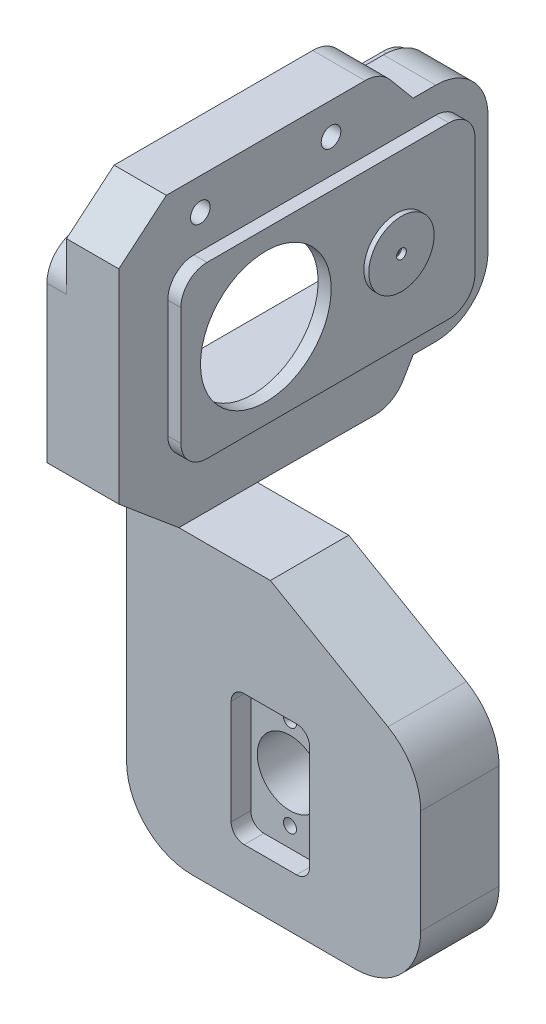
SolidWorks part; units mm, degrees
other "Markup1"
sketch "Sketch8" plane through (0, 0, -51.7836) normal (-1, 0, 0) x (0, 0, 1)
material "ABS"
ref_plane "Front Plane" through (0, 0, 0) normal (0, 0, 1) x (1, 0, 0)
ref_plane "Top Plane" through (0, 0, 0) normal (0, 1, 0) x (1, 0, 0)
ref_plane "Right Plane" through (0, 0, 0) normal (1, 0, 0) x (0, 0, -1)
sketch "Sketch1" plane through (0, 0, 0) normal (0, 0, 1) x (1, 0, 0)
  line L0 (0, 45) -> (0, 10)
  line L1 (10, 0) -> (35, 0)
  line L2 (45, 10) -> (45, 25.9474)
  line L3 (40, 34.6077) -> (22, 45)
  line L4 (22, 45) -> (0, 45)
  line L6 (18, 8) -> (26, 8)
  line L7 (16, 10) -> (16, 26)
  line L8 (18, 28) -> (26, 28)
  line L9 (28, 10) -> (28, 26)
  line L10 (16, 8) -> (28, 28) construction
  line L11 (16, 28) -> (28, 8) construction
  circle A0 centre (22, 18) radius 5
  circle A1 centre (22, 11) radius 1
  circle A2 centre (22, 25) radius 1
  arc A3 (18, 8) -> (16, 10) centre (18, 10) cw
  arc A4 (26, 8) -> (28, 10) centre (26, 10) ccw
  arc A5 (26, 28) -> (28, 26) centre (26, 26) cw
  arc A6 (16, 26) -> (18, 28) centre (18, 26) cw
  arc A11 (45, 25.9474) -> (40, 34.6077) centre (35, 25.9474) ccw
  arc A12 (0, 10) -> (10, 0) centre (10, 10) ccw
  arc A13 (35, 0) -> (45, 10) centre (35, 10) ccw
  point P44 (0, 0)
  point P47 (45, 0)
  dimension "D5" = 10
  dimension "D7" = 2
  dimension "D4" = 2
  dimension "D16" = 10
  dimension "D1" = 45
  dimension "D2" = 45
  dimension "D3" = 120
  dimension "D6" = 7
  dimension "D8" = 7
  dimension "D9" = 27
  dimension "D10" = 22
  dimension "D11" = 20
  dimension "D12" = 11
  dimension "D13" = 6
  dimension "D14" = 10
extrude "Boss-Extrude1" add sketch "Sketch1" against normal blind 12 contours L4 L0 A12 L1 A13 L2 A11 L3
extrude "Cut-Extrude1" cut sketch "Sketch1<3>" against normal blind 3 contours A2 | A6 L7 A3 L6 A4 L9 A5 L8 A2 A1 | A1 | A0 region at (16.7507, 8.7507, 0) region at (22, 11, 0) region at (22, 25, 0)
sketch "Sketch1<3>" plane through (0, 0, 0) normal (0, 0, 1) x (1, 0, 0) same geometry as "Sketch1"
extrude "Cut-Extrude2" cut sketch "Sketch1<4>" against normal through all contours A2 | A1 | A0 region at (22, 18, 0) region at (22, 11, 0) region at (22, 25, 0)
sketch "Sketch1<4>" plane through (0, 0, 0) normal (0, 0, 1) x (1, 0, 0) same geometry as "Sketch1"
sketch "Sketch3" plane through (0, 0, 0) normal (-1, 0, 0) x (0, 0, 1)
  line L0 (9.1925, 52.7135) -> (0, 45)
  line L1 (9.1925, 83.8935) -> (9.1925, 52.7135)
  line L2 (9.1925, 83.8935) -> (1.9151, 90)
  line L3 (1.9151, 90) -> (-28.4826, 90)
  line L4 (-32.3129, 88.2139) -> (-35.8509, 83.9975)
  line L6 (-41.3075, 76) -> (-41.3075, 58)
  line L8 (-34.3402, 47.4081) -> (-35.8509, 50)
  line L9 (-29.9998, 44.926) -> (-12, 45)
  line L10 (-0.3075, 76) -> (-0.3075, 58)
  line L15 (-47.3075, 75.9975) -> (-47.3075, 58)
  line L16 (-39.3075, 50) -> (-2.3075, 50)
  line L19 (5.6925, 75.9975) -> (5.6925, 58)
  line L21 (-12, 45) -> (0, 45)
  line L26 (-39.3075, 56) -> (-2.3075, 56)
  line L33 (-43.3075, 75.9975) -> (-43.3075, 58)
  line L34 (-39.3075, 54) -> (-2.3075, 54)
  line L35 (1.6925, 75.9975) -> (1.6925, 58)
  line L39 (-39.3075, 78) -> (-2.3075, 78)
  line L53 (-39.3075, 83.9975) -> (-2.3075, 83.9975)
  line L55 (-39.3075, 79.9975) -> (-2.3075, 79.9975)
  circle A0 centre (-11.3075, 67) radius 10
  arc A3 (-41.3075, 76) -> (-39.3075, 78) centre (-39.3075, 76) cw
  arc A5 (-34.3402, 47.4081) -> (-29.9998, 44.926) centre (-30.0204, 49.9259) ccw
  arc A12 (-43.3075, 75.9975) -> (-39.3075, 79.9975) centre (-39.3075, 75.9975) cw
  arc A14 (-0.3075, 58) -> (-2.3075, 56) centre (-2.3075, 58) cw
  arc A16 (-39.3075, 56) -> (-41.3075, 58) centre (-39.3075, 58) cw
  arc A21 (-43.3075, 58) -> (-39.3075, 54) centre (-39.3075, 58) ccw
  arc A22 (1.6925, 58) -> (-2.3075, 54) centre (-2.3075, 58) cw
  arc A23 (-2.3075, 79.9975) -> (1.6925, 75.9975) centre (-2.3075, 75.9975) cw
  arc A24 (-47.3075, 75.9975) -> (-39.3075, 83.9975) centre (-39.3075, 75.9975) cw
  circle A25 centre (-34.8075, 67) radius 5 construction
  arc A28 (-47.3075, 58) -> (-39.3075, 50) centre (-39.3075, 58) ccw
  arc A29 (-2.3075, 78) -> (-0.3075, 76) centre (-2.3075, 76) cw
  arc A32 (-28.4826, 90) -> (-32.3129, 88.2139) centre (-28.4826, 85) ccw
  arc A33 (5.6925, 58) -> (-2.3075, 50) centre (-2.3075, 58) cw
  arc A36 (-2.3075, 83.9975) -> (5.6925, 75.9975) centre (-2.3075, 75.9975) cw
  point P26 (-2.1748, 77.825)
  point P53 (-0.3075, 56.5128)
  line M15 (0, 45) -> (-12, 45)
  dimension "D4" = 11
  dimension "D13" = 130
  dimension "D15" = 53
  dimension "D18" = 10
  dimension "D8" = 25.9975
  dimension "D22" = 2
  dimension "D16" = 45
  dimension "D25" = 2
  dimension "D26" = 4
  dimension "D27" = 8
  dimension "D7" = 22
  dimension "D31" = 8
  dimension "D20" = 8
  dimension "D34" = 4
  dimension "D32" = 4
  dimension "D39" = 4
  dimension "D42" = 4
  dimension "D6" = 20
  dimension "D21" = 4
  dimension "D30" = 5
  dimension "D36" = 2
  dimension "D43" = 8
  dimension "D52" = 5
  dimension "D1" = 53
  dimension "D5" = 23.5
  dimension "D9" = 33.9975
  dimension "D10" = 45
  dimension "D11" = 45
  dimension "D12" = 9.5
  dimension "D14" = 12
  dimension "D17" = 41
  dimension "D19" = 6.5
  dimension "D24" = 4
  dimension "D28" = 12.5
  dimension "D29" = 5.5042
  dimension "D33" = 45
  dimension "D35" = 130
  dimension "D40" = 13
  dimension "D23" = 2
  dimension "D44" = 18
  dimension "D45" = 6
  dimension "D46" = 120
  dimension "D47" = 130
  dimension "D48" = 4
  dimension "D49" = 2
  dimension "D50" = 11
  dimension "D51" = 3
  dimension "D53" = 140
  dimension "D54" = 130
  dimension "D55" = 20.5
  dimension "D56" = 12.5
  dimension "D57" = 11
extrude "Boss-Extrude2" add sketch "Sketch3" against normal blind 8 contours L39 L10 L9 L0 L1 L2 L3 L4 M15 | L26 A0 L6 A3 L39 L10 | L19 L15 L16 L35 A22 L34 A21 L33 A12 region at (0, 49.3449, 4.1867) region at (0, 50.6297, -37.5792) region at (0, 78.4584, -41.7684)
extrude "Boss-Extrude3" add sketch "Sketch3<4>" against normal blind 10 contours A22 L35 A12 L33 A21 L34 L10 L26 L6 A3 L39 | L10 L39 A3 L6 L26 A0 | A0 region at (0, 67, -25.9144) region at (0, 78.4584, -41.7684) region at (0, 67, -11.3075)
sketch "Sketch3<4>" plane through (0, 0, 0) normal (-1, 0, 0) x (0, 0, 1) same geometry as "Sketch3"
extrude "Cut-Extrude5" cut sketch "Sketch3<6>" against normal blind 8 contours L26 L10 L39 A3 L6 A0 | A0 region at (0, 67, -25.9144) region at (0, 67, -11.3075)
sketch "Sketch3<6>" plane through (0, 0, 0) normal (-1, 0, 0) x (0, 0, 1) same geometry as "Sketch3"
extrude "Cut-Extrude6" cut sketch "Sketch3<7>" against normal through all contours A0 region at (0, 67, -11.3075)
sketch "Sketch3<7>" plane through (0, 0, 0) normal (-1, 0, 0) x (0, 0, 1) same geometry as "Sketch3"
sketch "Sketch7" plane through (0, 0, 0) normal (-1, 0, 0) x (0, 0, 1)
  line L0 (-41.3075, 76) -> (-41.3075, 58) construction
  line L1 (-0.3075, 76) -> (-0.3075, 58) construction
  line L2 (-39.3075, 56) -> (-2.3075, 56) construction
  circle A0 centre (-44.3075, 72) radius 1.2804
  circle A1 centre (-44.3075, 62) radius 1.2804
  circle A2 centre (2.6925, 62) radius 1.2804
  circle A3 centre (2.6925, 72) radius 1.2804
  dimension "D1" = 2.5608
  dimension "D2" = 3
  dimension "D3" = 3
  dimension "D4" = 3
  dimension "D5" = 10
  dimension "D6" = 6
extrude "Cut-Extrude7" cut sketch "Sketch7" against normal blind 3
sketch "Sketch11" plane through (8, 0, 0) normal (1, 0, 0) x (0, 0, -1)
  line L0 (39.3075, 79.9975) -> (2.3075, 79.9975) construction
  line L1 (-9.1925, 83.8935) -> (-9.1925, 52.7135) construction
  circle A0 centre (0.8075, 84.4975) radius 3
  circle A1 centre (24.8075, 84.4975) radius 3
  dimension "D1" = 6
  dimension "D5" = 6
  dimension "D2" = 4.5
  dimension "D3" = 24
  dimension "D4" = 10
sketch "Sketch9" plane through (8, 0, 0) normal (1, 0, 0) x (0, 0, -1)
  line L0 (13.2838, 90) -> (13.2838, 44.9947) construction
  line L1 (35.8509, 83.9975) -> (35.8509, 50) construction
  line L2 (39.3075, 79.9975) -> (2.3075, 79.9975) construction
  line L3 (-1.9151, 90) -> (28.4826, 90) construction
  line L4 (29.9998, 44.926) -> (12, 45) construction
  line L5 (47.3075, 66.9987) -> (-9.1925, 66.9987) construction
  line L6 (47.3075, 75.9975) -> (47.3075, 58) construction
  line L7 (-9.1925, 83.8935) -> (-9.1925, 52.7135) construction
  line L8 (19.0575, 90) -> (19.0575, 44.971) construction
  line L9 (13.3309, 90) -> (13.3309, 44.9945) construction
  circle A0 centre (3.2838, 85.1475) radius 1.5
  circle A1 centre (23.2838, 85.1475) radius 1.5
  dimension "D1" = 3
  dimension "D2" = 5.15
  dimension "D3" = 10
  dimension "D4" = 10
  dimension "D5" = 28.25
  dimension "D6" = 22.52
extrude "Cut-Extrude8" cut sketch "Sketch9" against normal through all both and the other way through all
sketch "Sketch12" plane through (10, 0, 0) normal (1, 0, 0) x (0, 0, -1)
  circle A0 centre (31.3075, 67) radius 0.5
  dimension "D1" = 1
  dimension "D2" = 20
extrude "Cut-Extrude9" cut sketch "Sketch12" against normal blind 10
sketch "Sketch13" plane through (10, 0, 0) normal (1, 0, 0) x (0, 0, -1)
  circle A0 centre (11.3075, 67) radius 10 construction
  circle A1 centre (31.3075, 67) radius 10 construction
  circle A2 centre (31.3075, 67) radius 5
  circle A3 centre (31.3075, 67) radius 0.75
  dimension "D1" = 20
  dimension "D2" = 10
  dimension "D3" = 1.5
extrude "Boss-Extrude5" add sketch "Sketch13" along normal blind 0.75 and the other way up to surface (2 mm away) other way up to face at (8, 67, -30.8075)
sketch "Sketch14" plane through (0, 0, 0) normal (-1, 0, 0) x (0, 0, 1)
  line L0 (-0.3075, 76) -> (-0.3075, 58) construction
  line L1 (-39.3075, 56) -> (-2.3075, 56) construction
  line L2 (-39.3075, 78) -> (-2.3075, 78) construction
  line L3 (-41.3075, 76) -> (-41.3075, 58) construction
  line L4 (-0.3075, 76) -> (-0.3075, 58)
  line L5 (-39.3075, 56) -> (-2.3075, 56)
  line L6 (-39.3075, 78) -> (-2.3075, 78)
  line L7 (-41.3075, 76) -> (-41.3075, 58)
  line L8 (-35.8509, 50) -> (5.9588, 50)
  line L9 (-45.1145, 81.5) -> (9.1925, 81.5)
  line L13 (0, 10) -> (0, 45)
  line L14 (0, 45) -> (9.1925, 52.7135)
  line L15 (9.1925, 52.7135) -> (9.1925, 83.8935)
  line L16 (9.1925, 83.8935) -> (1.9151, 90)
  line L17 (1.9151, 90) -> (-28.4826, 90)
  line L18 (-32.3129, 88.2139) -> (-35.8509, 83.9975)
  line L19 (-35.8509, 83.9975) -> (-39.3075, 83.9975)
  line L20 (-47.3075, 75.9975) -> (-47.3075, 58)
  line L21 (-39.3075, 50) -> (-35.8509, 50)
  line L22 (-35.8509, 50) -> (-34.3402, 47.4081)
  line L23 (-29.9998, 44.926) -> (-12, 45)
  line L24 (-12, 45) -> (-12, 10)
  line L25 (-12, 10) -> (0, 10)
  line L27 (5.9588, 50) -> (9.1925, 52.7135)
  line L28 (9.1925, 52.7135) -> (9.1925, 81.5)
  line L33 (-47.3075, 75.9975) -> (-47.3075, 58)
  line L34 (-39.3075, 50) -> (-35.8509, 50)
  arc A0 (-2.3075, 56) -> (-0.3075, 58) centre (-2.3075, 58) ccw construction
  arc A1 (-0.3075, 76) -> (-2.3075, 78) centre (-2.3075, 76) ccw construction
  arc A2 (-41.3075, 58) -> (-39.3075, 56) centre (-39.3075, 58) ccw construction
  arc A3 (-39.3075, 78) -> (-41.3075, 76) centre (-39.3075, 76) ccw construction
  arc A4 (-28.4826, 90) -> (-32.3129, 88.2139) centre (-28.4826, 85) ccw
  arc A5 (-39.3075, 83.9975) -> (-47.3075, 75.9975) centre (-39.3075, 75.9975) ccw
  arc A6 (-47.3075, 58) -> (-39.3075, 50) centre (-39.3075, 58) ccw
  arc A7 (-34.3402, 47.4081) -> (-29.9998, 44.926) centre (-30.0204, 49.9259) ccw
  arc A9 (-45.1145, 81.5) -> (-47.3075, 75.9975) centre (-39.3075, 75.9975) ccw
  arc A10 (-47.3075, 58) -> (-39.3075, 50) centre (-39.3075, 58) ccw
  circle A12 centre (-44.3075, 72) radius 1.2804 construction
  circle A13 centre (-44.3075, 62) radius 1.2804 construction
  circle A14 centre (2.6925, 62) radius 1.2804 construction
  circle A15 centre (2.6925, 72) radius 1.2804 construction
  arc A18 (-2.3075, 56) -> (-0.3075, 58) centre (-2.3075, 58) ccw
  arc A19 (-0.3075, 76) -> (-2.3075, 78) centre (-2.3075, 76) ccw
  arc A20 (-41.3075, 58) -> (-39.3075, 56) centre (-39.3075, 58) ccw
  arc A21 (-39.3075, 78) -> (-41.3075, 76) centre (-39.3075, 76) ccw
  circle A22 centre (-44.3075, 72) radius 1.2804
  circle A23 centre (-44.3075, 62) radius 1.2804
  circle A24 centre (2.6925, 62) radius 1.2804
  circle A25 centre (2.6925, 72) radius 1.2804
  dimension "D2" = 3.5
  dimension "D1" = 0
extrude "Boss-Extrude7" add sketch "Sketch14" along normal blind 3
sketch "Sketch15" [suppressed] plane through (0, 0, 0) normal (0, 0, 1) x (1, 0, 0)
  line L0 (-4, 10) -> (0, 10) construction
  line L1 (6, 0) -> (10.7457, 0)
  line L2 (-4, 10) -> (-4, 19.3711) construction
  line L3 (-4, 19.3711) -> (10.7457, 19.3711) construction
  line L4 (10.7457, 0) -> (10.7457, 19.3711) construction
  line L5 (-4, 0) -> (10.7457, 19.3711) construction
  line L6 (-4, 19.3711) -> (10.7457, 0) construction
  line L7 (-4, 10) -> (0, 10)
  arc A0 (-4, 10) -> (6, 0) centre (6, 10) ccw
  arc A1 (0, 10) -> (10, 0) centre (10, 10) ccw construction
  arc A2 (0, 10) -> (10, 0) centre (10, 10) ccw
  point P4 (3.3729, 9.6856)
  line M7 (-4, 10) -> (0, 10)
  arc M8 (0, 10) -> (10, 0) centre (10, 10) ccw
  dimension "D1" = 10
extrude "Boss-Extrude8" [suppressed] add sketch "Sketch15" against normal up to surface (12 mm away) contours A0 L1 M7 M8
fillet "Fillet1" radius 5 2 edges at (-1.5, 81.5, 9.1925) (-1.5, 81.5, -45.1145)
sketch "Sketch16" plane through (8, 0, 0) normal (-1, 0, 0) x (0, 0, 1)
  circle A0 centre (-31.3075, 67) radius 0.5 construction
  circle A1 centre (-31.3075, 67) radius 0.5
extrude "Boss-Extrude9" add sketch "Sketch16" against normal blind 1
sketch "Sketch17" plane through (8, 0, 0) normal (-1, 0, 0) x (0, 0, 1)
  circle A0 centre (-31.3075, 67) radius 2.5
  dimension "D1" = 5
extrude "Boss-Extrude10" add sketch "Sketch17" along normal blind 1.75
